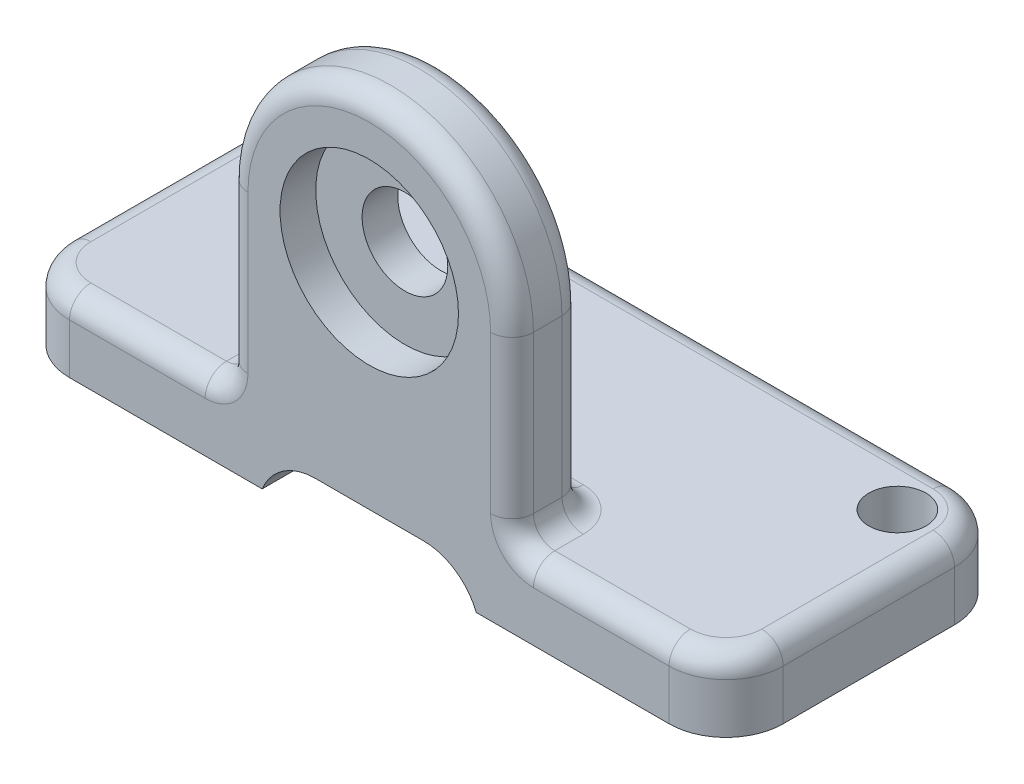
SolidWorks part; units mm, degrees
ref_plane "Спереди" through (0, 0, 0) normal (0, 0, 1) x (1, 0, 0)
ref_plane "Сверху" through (0, 0, 0) normal (0, 1, 0) x (1, 0, 0)
ref_plane "Справа" through (0, 0, 0) normal (1, 0, 0) x (0, 0, -1)
sketch "Эскиз3" plane through (0, 0, 0) normal (0, 1, 0) x (1, 0, 0)
  line L1 (0, 0) -> (100, 0)
  line L2 (0, 0) -> (0, 40)
  line L3 (0, 40) -> (100, 40)
  line L4 (100, 0) -> (100, 40)
  dimension "D1" = 100
  dimension "D2" = 40
extrude "Бобышка-Вытянуть1" add sketch "Эскиз3" along normal blind 10
sketch "Эскиз6" plane through (0, 0, 0) normal (0, 0, 1) x (1, 0, 0)
  line L0 (30, 0) -> (30, 35)
  line L1 (0, 0) -> (100, 0) construction
  line L2 (70, 35) -> (70, 0)
  line L3 (70, 0) -> (30, 0)
  arc A0 (30, 35) -> (70, 35) centre (50, 35) cw
  dimension "D1" = 35
  dimension "D3" = 20
  dimension "D2" = 50
extrude "Бобышка-Вытянуть2" add sketch "Эскиз6" against normal blind 10
sketch "Эскиз7" plane through (0, 0, 0) normal (0, 0, 1) x (1, 0, 0)
  circle A0 centre (50, 35) radius 12.5
  arc A1 (70, 35) -> (30, 35) centre (50, 35) ccw construction
  dimension "D1" = 25
extrude "Вырез-Вытянуть1" cut sketch "Эскиз7" against normal blind 5
sketch "Эскиз8" plane through (0, 0, -5) normal (0, 0, 1) x (1, 0, 0)
  circle A0 centre (50, 35) radius 6
  circle A1 centre (50, 35) radius 12.5 construction
  dimension "D1" = 12
extrude "Вырез-Вытянуть2" cut sketch "Эскиз8" against normal through all
sketch "Эскиз9" plane through (0, 0, 0) normal (0, 0, 1) x (1, 0, 0)
  line L0 (0, 0) -> (100, 0) construction
  line L1 (35, 0) -> (65, 0)
  line L2 (35, 0) -> (35, 5)
  line L3 (35, 5) -> (65, 5)
  line L4 (65, 0) -> (65, 5)
  line L5 (0, 10) -> (0, 0) construction
  dimension "D1" = 30
  dimension "D2" = 5
  dimension "D3" = 35
extrude "Вырез-Вытянуть3" cut sketch "Эскиз9" against normal through all
fillet "Скругление1" radius 8 6 edges at (0, 5, 0) (0, 5, -40) (35, 5, -20) (65, 5, -20) (100, 5, -40) (100, 5, 0)
sketch "Эскиз10" plane through (0, 10, 0) normal (0, 1, 0) x (1, 0, 0)
  line L0 (92, 40) -> (8, 40) construction
  line L1 (50, 40) -> (50, -8.1019) construction
  circle A0 centre (8, 32) radius 4
  circle A1 centre (92, 32) radius 4
  dimension "D1" = 8
  dimension "D2" = 42
  dimension "D3" = 8
extrude "Вырез-Вытянуть4" cut sketch "Эскиз10" against normal through all
fillet "Скругление2" radius 3 18 edges at (30, 10, -5) (50, 10, -10) (70, 22.5, -10) (30, 22.5, -10) (70, 22.5, 0) (30, 22.5, 0) (19, 10, 0) (2.3431, 10, -2.3431) (0, 10, -20) (2.3431, 10, -37.6569) (50, 10, -40) (97.6569, 10, -37.6569) (100, 10, -20) (97.6569, 10, -2.3431) (70, 10, -5) (50, 55, -10) (50, 55, 0) (81, 10, 0)
